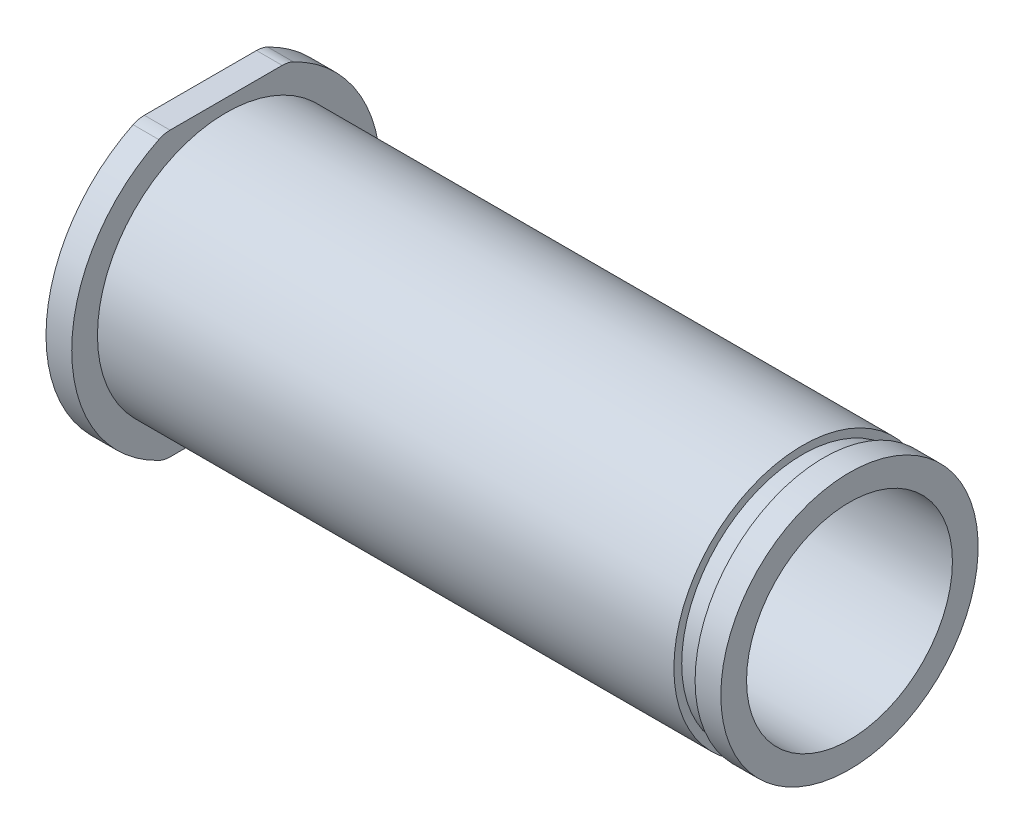
SolidWorks part; units mm, degrees
material "6061 Alloy"
ref_plane "Front Plane" through (0, 0, 0) normal (0, 0, 1) x (1, 0, 0)
ref_plane "Top Plane" through (0, 0, 0) normal (0, 1, 0) x (1, 0, 0)
ref_plane "Right Plane" through (0, 0, 0) normal (1, 0, 0) x (0, 0, -1)
sketch "Sketch1" plane through (0, 0, 0) normal (0, 0, 1) x (1, 0, 0)
  line L0 (0, 0) -> (80.0862, 0) construction
  line L1 (0, 19.05) -> (0, 12.7)
  line L2 (0, 12.7) -> (80.0862, 12.7)
  line L3 (80.0862, 12.7) -> (80.0862, 15.875)
  line L4 (80.0862, 15.875) -> (76.9112, 15.875)
  line L5 (76.9112, 15.875) -> (76.9112, 14.9098)
  line L6 (76.9112, 14.9098) -> (74.295, 14.9098)
  line L7 (74.295, 14.9098) -> (74.295, 15.875)
  line L8 (74.295, 15.875) -> (3.175, 15.875)
  line L9 (3.175, 15.875) -> (3.175, 19.05)
  line L10 (3.175, 19.05) -> (0, 19.05)
  dimension "D1" = 3.175
  dimension "D2" = 3.175
  dimension "D3" = 31.75
  dimension "D4" = 29.8196
  dimension "D5" = 2.6162
  dimension "D6" = 38.1
  dimension "D7" = 25.4
  dimension "D8" = 71.12
revolve "Revolve1" add sketch "Sketch1" angle 360 about L0
sketch "Sketch2" plane through (0, 0, 0) normal (-1, 0, 0) x (0, 0, 1)
  line L0 (0, 17.4625) -> (0, -17.4625) construction
  line L1 (-7.6134, 17.4625) -> (7.6134, 17.4625)
  line L2 (-7.6134, 17.4625) -> (-7.6134, 19.05)
  line L3 (-7.6134, 19.05) -> (7.6134, 19.05)
  line L4 (7.6134, 17.4625) -> (7.6134, 19.05)
  line L6 (-7.6134, -17.4625) -> (7.6134, -17.4625)
  line L7 (-7.6134, -17.4625) -> (-7.6134, -19.05)
  line L8 (-7.6134, -19.05) -> (7.6134, -19.05)
  line L9 (7.6134, -17.4625) -> (7.6134, -19.05)
  circle A0 centre (0, 0) radius 19.05 construction
  dimension "D1" = 38.1
  dimension "D2" = 34.925
extrude "Cut-Extrude1" cut sketch "Sketch2" against normal through all
fillet "Fillet1" radius 3.175 4 edges at (1.5875, -17.4625, -7.6134) (1.5875, -17.4625, 7.6134) (1.5875, 17.4625, 7.6134) (1.5875, 17.4625, -7.6134)
